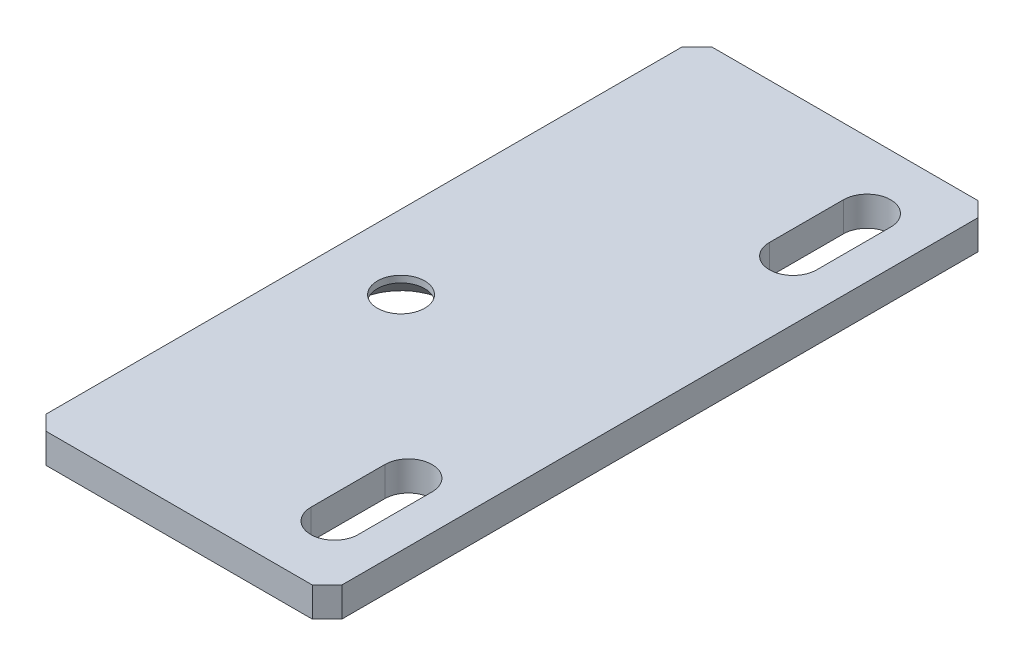
SolidWorks part; units mm, degrees
material "6061 Alloy"
ref_plane "Front Plane" through (0, 0, 0) normal (0, 0, 1) x (1, 0, 0)
ref_plane "Top Plane" through (0, 0, 0) normal (0, 1, 0) x (1, 0, 0)
ref_plane "Right Plane" through (0, 0, 0) normal (1, 0, 0) x (0, 0, -1)
sketch "Sketch1" plane through (0, 0, 0) normal (0, 1, 0) x (1, 0, 0)
  line L5 (10, -22.5) -> (-10, -22.5)
  line L6 (10, -22.5) -> (10, 22.5)
  line L7 (10, 22.5) -> (-10, 22.5)
  line L8 (-10, -22.5) -> (-10, 22.5)
  line L9 (10, -22.5) -> (-10, 22.5) construction
  line L10 (10, 22.5) -> (-10, -22.5) construction
  point P0 (0, 0)
  dimension "D3" = 20
  dimension "D4" = 45
extrude "Base" add sketch "Sketch1" along normal blind 2
sketch "Sketch6" plane through (0, 2, 0) normal (0, 1, 0) x (1, 0, 0)
  line L0 (6, 18) -> (6, 13) construction
  line L1 (7.6, 18) -> (7.6, 13)
  line L2 (4.4, 18) -> (4.4, 13)
  line L3 (6, -13) -> (6, -18) construction
  line L4 (7.6, -13) -> (7.6, -18)
  line L5 (4.4, -13) -> (4.4, -18)
  line L6 (0, 0) -> (-4.8321, 0) construction
  line L7 (10, -22.5) -> (10, 22.5) construction
  arc A0 (7.6, 18) -> (4.4, 18) centre (6, 18) ccw
  arc A1 (4.4, 13) -> (7.6, 13) centre (6, 13) ccw
  arc A2 (7.6, -13) -> (4.4, -13) centre (6, -13) ccw
  arc A3 (4.4, -18) -> (7.6, -18) centre (6, -18) ccw
  point P3 (6, 15.5)
  point P8 (6, -15.5)
  dimension "D1" = 3.2
  dimension "D2" = 5
  dimension "D3" = 31
  dimension "D4" = 4
extrude "ScrewSlots" cut sketch "Sketch6" against normal through all
hole_wizard "PulleyHole" positions "Sketch4" profile "Sketch5" countersink size "M3" standard "ANSI Metric" end condition through all
sketch "Sketch4" plane through (0, 0, 0) normal (0, -1, 0) x (-1, 0, 0)
  line L2 (-10, -22.5) -> (-10, 22.5) construction
  line L3 (10, -22.5) -> (-10, -22.5) construction
  point P0 (5, -2.5)
  point P7 (-1.2986, -2.1363)
  dimension "D1" = 20
  dimension "D2" = 15
sketch "Sketch5" plane through (-5, 0, 2.5) normal (1, 0, 0) x (0, 0, -1)
  line L0 (0, 0) -> (0, 2)
  line L1 (0, 2) -> (1.6, 2)
  line L2 (1.6, 2) -> (1.6, 1.55)
  line L3 (1.6, 1.55) -> (3.15, 0)
  line L5 (3.15, 0) -> (0, 0)
  line L6 (-1.6, 1.55) -> (-3.15, 0) construction
  line L11 (0, -6.35) -> (0, 107.95) construction
  dimension "Thru Hole Dia." = 3.2
  dimension "Thru Hole Depth" = 2
  dimension "Near C'Sink Dia." = 6.3
  dimension "Near C'Sink Angle" = 90
chamfer "Chamfer1" distance 1 angle 45 4 edges at (-10, 1, -22.5) (10, 1, -22.5) (10, 1, 22.5) (-10, 1, 22.5)
